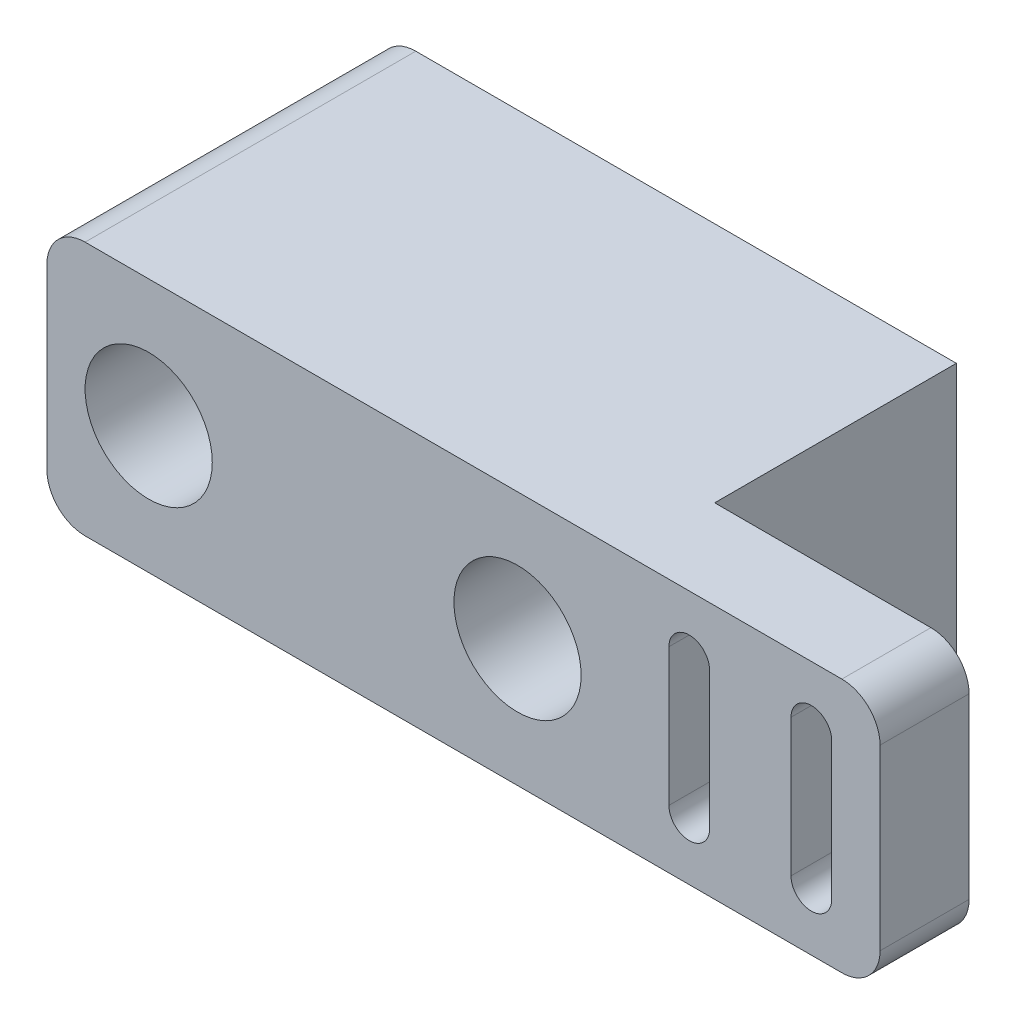
SolidWorks part; units mm, degrees
material "ABS"
ref_plane "Front Plane" through (0, 0, 0) normal (0, 0, 1) x (1, 0, 0)
ref_plane "Top Plane" through (0, 0, 0) normal (0, 1, 0) x (1, 0, 0)
ref_plane "Right Plane" through (0, 0, 0) normal (1, 0, 0) x (0, 0, -1)
sketch "Sketch1" plane through (0, 0, 0) normal (0, 0, 1) x (1, 0, 0)
  line L0 (48.9, 15.4) -> (48.9, 4.6)
  line L1 (3, 0) -> (62.5, 0)
  line L2 (0, 3) -> (0, 17)
  line L3 (3, 20) -> (62.5, 20)
  line L4 (65.5, 3) -> (65.5, 17)
  line L5 (52.1, 15.4) -> (52.1, 4.6)
  line L6 (0, 10) -> (65.5, 10) construction
  line L7 (58.5, 15.4) -> (58.5, 4.6)
  line L8 (61.7, 15.4) -> (61.7, 4.6)
  circle A0 centre (8, 10) radius 5 construction
  circle A1 centre (37, 10) radius 5 construction
  arc A2 (52.1, 15.4) -> (48.9, 15.4) centre (50.5, 15.4) ccw
  arc A3 (48.9, 4.6) -> (52.1, 4.6) centre (50.5, 4.6) ccw
  arc A4 (61.7, 15.4) -> (58.5, 15.4) centre (60.1, 15.4) ccw
  arc A5 (58.5, 4.6) -> (61.7, 4.6) centre (60.1, 4.6) ccw
  arc A6 (62.5, 20) -> (65.5, 17) centre (62.5, 17) cw
  arc A7 (65.5, 3) -> (62.5, 0) centre (62.5, 3) cw
  arc A8 (3, 0) -> (0, 3) centre (3, 3) cw
  arc A9 (0, 17) -> (3, 20) centre (3, 17) cw
  circle A10 centre (8, 10) radius 2.6
  circle A11 centre (37, 10) radius 2.6
  point P19 (52.1, 10)
  point P26 (65.5, 20)
  point P31 (0, 0)
  point P34 (0, 20)
  dimension "D3" = 3.2
  dimension "D7" = 10
  dimension "D8" = 8
  dimension "D9" = 29
  dimension "D10" = 3
  dimension "D11" = 5.2
  dimension "D1" = 65.5
  dimension "D2" = 20
  dimension "D4" = 10.8
  dimension "D5" = 13.4
  dimension "D6" = 2
extrude "Boss-Extrude1" add sketch "Sketch1" against normal blind 7
sketch "Sketch2" plane through (0, 0, -7) normal (0, 0, -1) x (-1, 0, 0)
  line L0 (-45.5, 20) -> (-45.5, 0)
  line L1 (-62.5, 20) -> (-3, 20) construction
  line L2 (-3, 0) -> (-62.5, 0) construction
  line L3 (0, 17) -> (0, 3) construction
  line L4 (-45.5, 20) -> (-3, 20)
  line L5 (0, 17) -> (0, 3)
  line L6 (-3, 0) -> (-45.5, 0)
  line L7 (-65.5, 3) -> (-65.5, 17) construction
  arc A0 (0, 17) -> (-3, 20) centre (-3, 17) ccw construction
  arc A1 (-3, 0) -> (0, 3) centre (-3, 3) ccw construction
  arc A2 (0, 17) -> (-3, 20) centre (-3, 17) ccw
  arc A3 (-3, 0) -> (0, 3) centre (-3, 3) ccw
  dimension "D1" = 20
extrude "Boss-Extrude2" add sketch "Sketch2" along normal blind 19
sketch "Sketch3" plane through (0, 0, -7) normal (0, 0, 1) x (1, 0, 0)
  circle A0 centre (8, 10) radius 2.6 construction
  circle A1 centre (37, 10) radius 2.6 construction
  circle A2 centre (8, 10) radius 2.6
  circle A3 centre (37, 10) radius 2.6
extrude "Cut-Extrude1" cut sketch "Sketch3" against normal up to surface (19 mm away) up to face at (15.9596, 10, -26)
sketch "Sketch4" plane through (0, 0, 0) normal (0, 0, 1) x (1, 0, 0)
  circle A0 centre (8, 10) radius 5
  circle A1 centre (37, 10) radius 5
  dimension "D1" = 10
extrude "Cut-Extrude2" cut sketch "Sketch4" against normal blind 14
